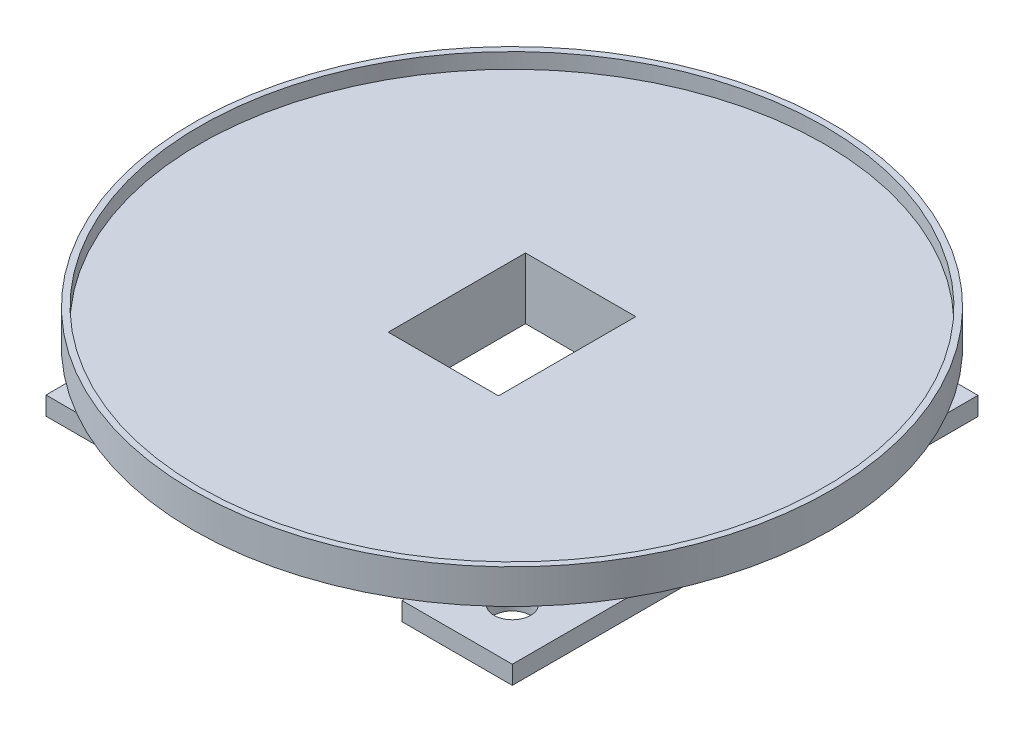
SolidWorks part; units mm, degrees
ref_plane "Front Plane" through (0, 0, 0) normal (0, 0, 1) x (1, 0, 0)
ref_plane "Top Plane" through (0, 0, 0) normal (0, 1, 0) x (1, 0, 0)
ref_plane "Right Plane" through (0, 0, 0) normal (1, 0, 0) x (0, 0, -1)
sketch "Sketch7" plane through (0, 0, 0) normal (0, -1, 0) x (1, 0, 0)
  line L7 (-4.5, -5.6) -> (4.5, -5.6)
  line L8 (-4.5, -5.6) -> (-4.5, 5.6)
  line L9 (-4.5, 5.6) -> (4.5, 5.6)
  line L10 (4.5, -5.6) -> (4.5, 5.6)
  line L11 (-4.5, -5.6) -> (4.5, 5.6) construction
  line L12 (-4.5, 5.6) -> (4.5, -5.6) construction
  circle A0 centre (0, 0) radius 25.5
  point P0 (0, 0)
  point P5 (0, 0)
  dimension "D1" = 51
  dimension "D2" = 11.2
  dimension "D4" = 9
extrude "Lens Spacer" add sketch "Sketch7" along normal blind 5
sketch "Sketch5" plane through (0, -5, 0) normal (0, -1, 0) x (-1, 0, 0)
  line L0 (-1000, 0) -> (49000, 0) construction
  line L1 (-19.025, -19) -> (-10.025, -19)
  line L2 (-19.025, -19) -> (-19.025, 19)
  line L3 (-19.025, 19) -> (-10.025, 19)
  line L12 (19.025, -19) -> (19.025, 19)
  line L13 (0, 5.6) -> (0, -5.6) construction
  line L14 (-19.025, 19) -> (-19.025, -19) construction
  line L19 (10.025, -19) -> (19.025, -19)
  line L20 (-19.025, -19) -> (19.025, -19) construction
  line L21 (10.025, 19) -> (10.025, -19)
  line L22 (10.025, 19) -> (19.025, 19)
  line L25 (-10.025, 19) -> (-10.025, -19)
  line L26 (19.025, -19) -> (19.025, 19) construction
  line L27 (19.025, 19) -> (-19.025, 19) construction
  line L30 (4.5, 5.6) -> (-4.5, 5.6) construction
  line L31 (-4.5, -5.6) -> (4.5, -5.6) construction
  line L32 (-19.025, 19) -> (19.025, -19) construction
  line L33 (-19.025, -19) -> (19.025, 19) construction
  circle A2 centre (-14.825, 14.8) radius 1.5
  circle A3 centre (-14.825, -14.8) radius 1.5
  circle A6 centre (15.175, -14.8) radius 1.5
  circle A7 centre (15.175, 14.8) radius 1.5
  point P27 (0, 5.6)
  point P32 (0, -5.6)
  point P35 (0, 0)
  dimension "D5" = 4.2
  dimension "D6" = 4.2
  dimension "D8" = 3
  dimension "D1" = 30
  dimension "D2" = 4.2
  dimension "D3" = 38.05
  dimension "D4" = 38
  dimension "D9" = 38
  dimension "D10" = 9
  dimension "D11" = 9
  dimension "D7" = 2
extrude "Attachment Legs" add sketch "Sketch5" along normal blind 1.5 contours A2 | A3 | L3 L25 L1 L2 | L21 L19 L12 L22 | A7 | A6 region at (14.825, -5, -14.8) region at (14.825, -5, 14.8)
sketch "Sketch8" plane through (0, 0, 0) normal (0, 1, 0) x (1, 0, 0)
  circle A0 centre (0, 0) radius 26
  circle A1 centre (0, 0) radius 25.5
  circle A2 centre (0, 0) radius 25.5
  dimension "D2" = 0.5
  dimension "D1" = 0
extrude "Lens Positioner" add sketch "Sketch8" along normal blind 1.25 and the other way up to surface (5 mm away) other way up to face at (-22.2625, -5, 0)
sketch "Sketch11" plane through (0, -6.5, 0) normal (0, -1, 0) x (1, 0, 0)
  line L1 (12.8686, -7.6239) -> (16.8686, -7.6239)
  line L2 (12.8686, -7.6239) -> (12.8686, -10.6239)
  line L3 (12.8686, -10.6239) -> (16.8686, -10.6239)
  line L7 (10.025, 19) -> (10.025, -19)
  line L12 (16.8686, -7.6239) -> (16.8686, -10.6239)
  line L13 (12.8686, -7.6239) -> (16.8686, -10.6239) construction
  line L14 (12.8686, -10.6239) -> (16.8686, -7.6239) construction
  line L15 (10.025, 19) -> (10.025, -19)
  line L16 (10.025, -19) -> (19.025, -19)
  line L20 (10.025, -19) -> (19.025, -19)
  line L23 (19.025, -19) -> (19.025, 19)
  line L25 (19.025, -19) -> (19.025, 19)
  line L26 (19.025, 19) -> (10.025, 19)
  line L27 (19.025, 19) -> (10.025, 19)
  point P2 (14.8686, -9.1239)
  dimension "D3" = 4
  dimension "D4" = 3
  dimension "D1" = 0
extrude "Node Hole" cut sketch "Sketch11" against normal blind 0.7 contours L2 L1 L12 L3
sketch "Sketch13" plane through (0, 0, 0) normal (0, 0, 1) x (1, 0, 0)
  line L1 (-26, 1.25) -> (-26, -5) construction
  line L2 (-17.7482, -5) -> (17.7482, -5) construction
  line L3 (-16, -5) -> (-26, -5)
  line L4 (-26, -5) -> (-26, -1.55)
  line L5 (26, 1.25) -> (-26, 1.25) construction
  circle A3 centre (-19.6577, -11.5476) radius 7.5
  arc A4 (-16, -5) -> (-26, -1.55) centre (-30.6308, -31.1904) ccw
  dimension "D3" = 30
  dimension "D4" = 7.5
  dimension "D1" = 2.8
  dimension "D2" = 10
revolve "Cut-Revolve1" cut sketch "Sketch13" angle 360 about axis through (0, -78.5391, 0) along (0, 1, 0) region at (-19.6577, -4.6169, 0) region at (-23.198, -3.4649, 0)
